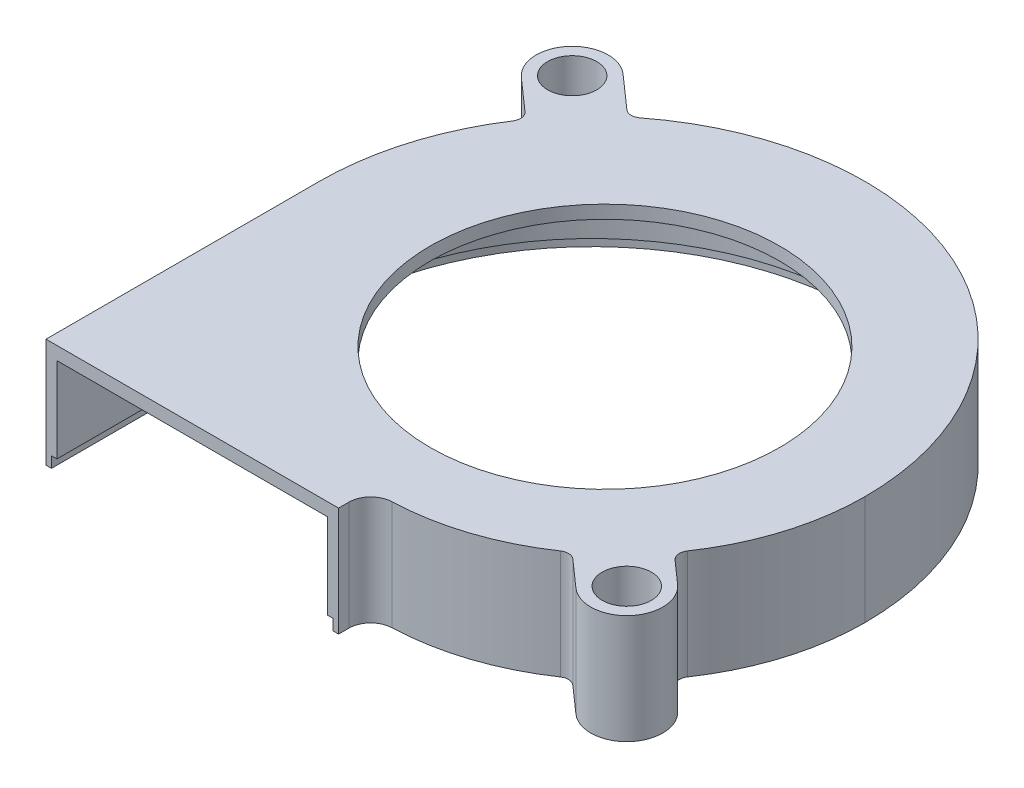
SolidWorks part; units mm, degrees
material "PET"
ref_plane "Спереди" through (0, 0, 0) normal (0, 0, 1) x (1, 0, 0)
ref_plane "Сверху" through (0, 0, 0) normal (0, 1, 0) x (1, 0, 0)
ref_plane "Справа" through (0, 0, 0) normal (1, 0, 0) x (0, 0, -1)
sketch "Эскиз1" plane through (0, 0, 0) normal (0, 1, 0) x (1, 0, 0)
  line L0 (0, -37.0288) -> (0, 52.769) construction
  line L1 (-41.2177, 0) -> (28.9689, 0) construction
  line L2 (-26.2, -25) -> (0.6, -25)
  line L3 (0.6, -25) -> (0.6, -24.0524)
  line L4 (-26.2, -25) -> (-26.2, 0)
  line L5 (17.8147, -20.4728) -> (22.1853, -15.5272) construction
  line L6 (-25.1853, 17.5272) -> (-20.8147, 22.4728) construction
  line L7 (-23, 20) -> (20, -18) construction
  line L8 (-20.8147, 22.4728) -> (-17.808, 19.8156)
  line L9 (-25.1853, 17.5272) -> (-22.3115, 14.9876)
  line L10 (17.8147, -20.4728) -> (15.377, -18.3185)
  line L11 (22.1853, -15.5272) -> (20.1437, -13.7231)
  circle A0 centre (0, 0) radius 16
  arc A1 (23.8, 0) -> (-16.5325, 19.7751) centre (-1.2, 0.0288) ccw
  circle A2 centre (-23, 20) radius 2.25
  circle A3 centre (20, -18) radius 2.25
  arc A4 (23.8, 0) -> (19.9791, -12.4113) centre (1.7319, 0) cw
  arc A5 (22.1853, -15.5272) -> (17.8147, -20.4728) centre (20, -18) cw
  arc A6 (-25.1853, 17.5272) -> (-20.8147, 22.4728) centre (-23, 20) cw
  arc A7 (14.152, -18.2412) -> (2.5279, -22.0537) centre (1.7319, 0) cw
  arc A8 (-22.1362, 13.6917) -> (-26.2, 0) centre (-1.2, 0.0288) ccw
  arc A9 (2.5279, -22.0537) -> (0.6, -24.0524) centre (2.6, -24.0524) ccw
  arc A10 (-17.808, 19.8156) -> (-16.5325, 19.7751) centre (-17.1458, 20.565) ccw
  arc A11 (-22.3115, 14.9876) -> (-22.1362, 13.6917) centre (-22.9737, 14.2383) cw
  arc A12 (20.1437, -13.7231) -> (19.9791, -12.4113) centre (20.8059, -12.9738) cw
  arc A13 (15.377, -18.3185) -> (14.152, -18.2412) centre (14.7148, -19.0678) ccw
  point P14 (0, 25)
  point P16 (16, 0)
  point P17 (0, -22)
  point P20 (23.8, 0)
  point P26 (0, -16)
  point P34 (-21.6527, 14.4054)
  point P41 (14.784, -17.7945)
  dimension "D1" = 18
  dimension "D2" = 20
  dimension "D8" = 50
  dimension "D11" = 3.3
  dimension "D12" = 7.8
  dimension "D13" = 6
  dimension "D14" = 2
  dimension "D5" = 4.5
  dimension "D6" = 32
  dimension "D15" = 1
  dimension "D3" = 23
  dimension "D4" = 20
  dimension "D7" = 50
  dimension "D9" = 26.8
  dimension "D10" = 25
extrude "Бобышка-Вытянуть1" add sketch "Эскиз1" against normal blind 10
sketch "Эскиз2" plane through (0, -10, 0) normal (0, -1, 0) x (-1, 0, 0)
  line L12 (-0.6, -25) -> (-0.6, -24.0524) construction
  line L13 (26.2, 0) -> (26.2, -25) construction
  line L14 (-0.6, -25) -> (-0.6, -24.0524) construction
  line L15 (26.2, 0) -> (26.2, -25) construction
  line L16 (0.4, -25) -> (0.4, -24.0524)
  line L17 (25.2, 0.0006) -> (25.2, -25)
  line L18 (25.2, -25) -> (0.4, -25)
  arc A19 (16.5325, 19.7751) -> (-23.8, 0) centre (1.2, 0.0288) ccw construction
  arc A20 (-23.8, 0) -> (-19.9791, -12.4113) centre (-1.7319, 0) ccw construction
  arc A21 (-14.152, -18.2412) -> (-2.5279, -22.0537) centre (-1.7319, 0) ccw construction
  arc A22 (-0.6, -24.0524) -> (-2.5279, -22.0537) centre (-2.6, -24.0524) ccw construction
  arc A23 (26.2, 0) -> (22.1362, 13.6917) centre (1.2, 0.0288) ccw construction
  arc A24 (16.5325, 19.7751) -> (-23.8, 0) centre (1.2, 0.0288) ccw construction
  arc A25 (-23.8, 0) -> (-19.9791, -12.4113) centre (-1.7319, 0) ccw construction
  arc A26 (-14.152, -18.2412) -> (-2.5279, -22.0537) centre (-1.7319, 0) ccw construction
  arc A27 (-0.6, -24.0524) -> (-2.5279, -22.0537) centre (-2.6, -24.0524) ccw construction
  arc A28 (26.2, 0) -> (22.1362, 13.6917) centre (1.2, 0.0288) ccw construction
  arc A29 (16.5325, 19.7751) -> (22.1362, 13.6917) centre (1.2, 0.0288) cw construction
  arc A30 (-19.9791, -12.4113) -> (-14.152, -18.2412) centre (-1.7319, 0) ccw construction
  arc A31 (0.4, -24.0524) -> (-2.4918, -21.0544) centre (-2.6, -24.0524) ccw
  arc A32 (-13.5892, -17.4146) -> (-2.4918, -21.0544) centre (-1.7319, 0) ccw
  arc A33 (-19.1522, -11.8489) -> (-13.5892, -17.4146) centre (-1.7319, 0) ccw
  arc A34 (-22.8, 0.0006) -> (-19.1522, -11.8489) centre (-1.7319, 0) ccw
  arc A35 (15.9192, 18.9852) -> (-22.8, 0.0006) centre (1.2, 0.0288) ccw
  arc A36 (15.9192, 18.9852) -> (21.2988, 13.1452) centre (1.2, 0.0288) cw
  arc A37 (25.2, 0.0006) -> (21.2988, 13.1452) centre (1.2, 0.0288) ccw
  dimension "D1" = 1
extrude "Вырез-Вытянуть1" cut sketch "Эскиз2" against normal offset from surface (8.8 mm away) 1.2 up to face at (0, 0, 16)
sketch "Эскиз11" plane through (0, -10, 0) normal (0, -1, 0) x (1, 0, 0)
  line L0 (-0.4, 24.0524) -> (-0.4, 25) construction
  line L1 (-25.2, 25) -> (-25.2, -0.0006) construction
  line L2 (-0.4, 24.0524) -> (-0.4, 25)
  line L3 (-25.2, 25) -> (-25.2, -0.0006)
  line L4 (-25.7, 25) -> (-25.7, -0.0003)
  line L5 (0.1, 24.0524) -> (0.1, 25)
  line L6 (-25.7, 25) -> (-25.2, 25)
  line L7 (-0.4, 25) -> (0.1, 25)
  arc A0 (-0.4, 24.0524) -> (2.4918, 21.0544) centre (2.6, 24.0524) ccw construction
  arc A1 (22.8, -0.0006) -> (2.4918, 21.0544) centre (1.7319, 0) ccw construction
  arc A2 (-25.2, -0.0006) -> (22.8, -0.0006) centre (-1.2, -0.0288) ccw construction
  arc A3 (-0.4, 24.0524) -> (2.4918, 21.0544) centre (2.6, 24.0524) ccw
  arc A4 (22.8, -0.0006) -> (2.4918, 21.0544) centre (1.7319, 0) ccw
  arc A5 (-25.2, -0.0006) -> (22.8, -0.0006) centre (-1.2, -0.0288) ccw
  arc A6 (-25.7, -0.0003) -> (23.3, -0.0003) centre (-1.2, -0.0288) ccw
  arc A7 (23.3, -0.0003) -> (2.5098, 21.554) centre (1.7319, 0) ccw
  arc A8 (0.1, 24.0524) -> (2.5098, 21.554) centre (2.6, 24.0524) ccw
  dimension "D1" = 0.5
extrude "Вырез-Вытянуть8" cut sketch "Эскиз11" against normal blind 1
